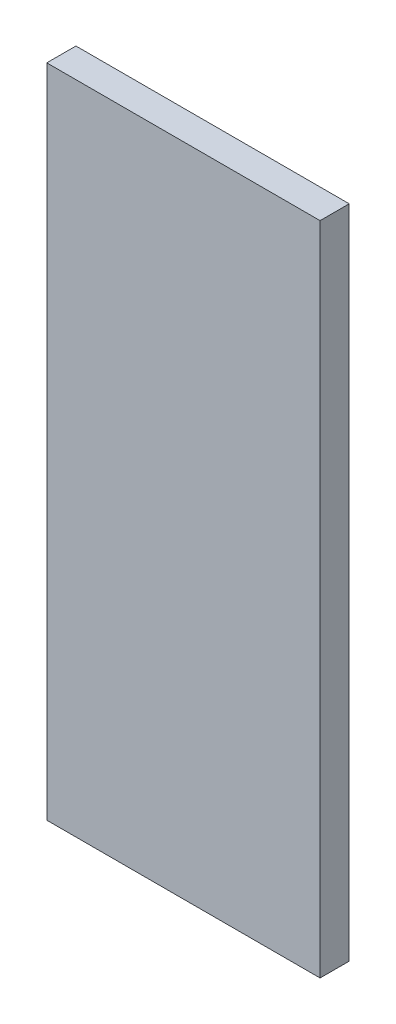
SolidWorks part; units mm, degrees
material "Простая углеродистая сталь"
ref_plane "Спереди" through (0, 0, 0) normal (0, 0, 1) x (1, 0, 0)
ref_plane "Сверху" through (0, 0, 0) normal (0, 1, 0) x (1, 0, 0)
ref_plane "Справа" through (0, 0, 0) normal (1, 0, 0) x (0, 0, -1)
sketch "Эскиз1" plane through (0, 0, 0) normal (0, 0, 1) x (1, 0, 0)
  line L1 (0, 0) -> (75, 0)
  line L2 (0, 0) -> (0, -180)
  line L3 (0, -180) -> (75, -180)
  line L4 (75, 0) -> (75, -180)
  dimension "D1" = 180
  dimension "D2" = 75
base flange "Базовая кромка1" sketch "Эскиз1" thickness 8 reverse thickness direction no parameters "D1"=3
sketch "Сгиб-Линии1" plane through (0, 0, 0) normal (0, 1, 0) x (1, 0, 0)
sketch "Граничная рамка1" plane through (0, 0, 0) normal (0, 1, 0) x (1, 0, 0)
sheet metal parameters "Листовой металл1" thickness 8 parameters "D1"=3
flat pattern "Развертка1" [suppressed]
sketch "Сгиб-Линии2" plane through (0, 0, 0) normal (0, 1, 0) x (1, 0, 0)
sketch "Граничная рамка2" [suppressed] plane through (0, 0, 0) normal (0, 1, 0) x (1, 0, 0)
